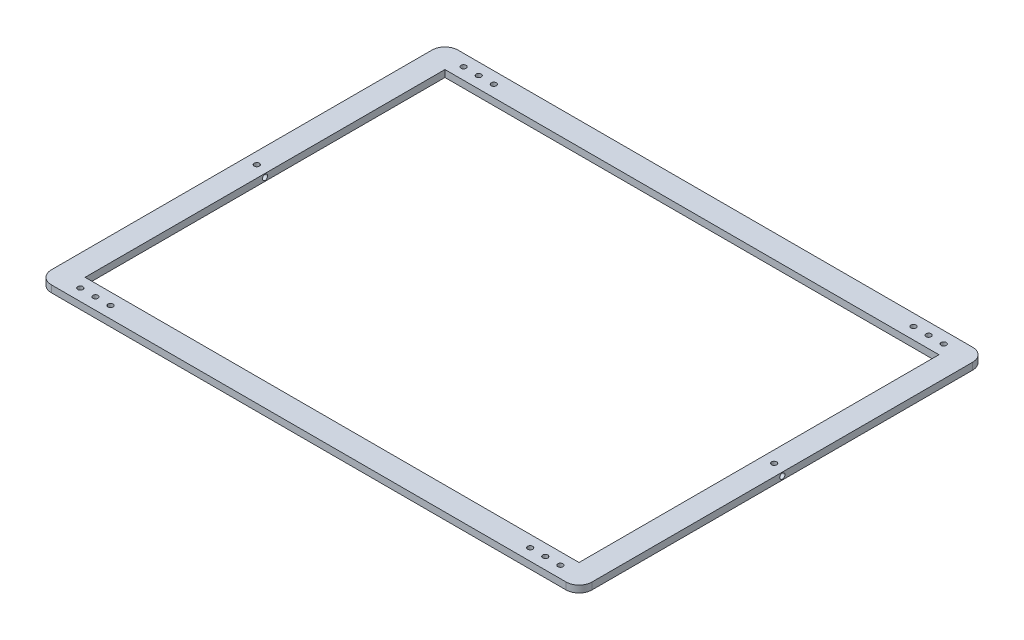
SolidWorks part; units mm, degrees
ref_plane "Спереди" through (0, 0, 0) normal (0, 0, 1) x (1, 0, 0)
ref_plane "Сверху" through (0, 0, 0) normal (0, 1, 0) x (1, 0, 0)
ref_plane "Справа" through (0, 0, 0) normal (1, 0, 0) x (0, 0, -1)
sketch "Эскиз1" plane through (0, 0, 0) normal (0, 1, 0) x (1, 0, 0)
  line L0 (0, 235) -> (0, -235) construction
  line L1 (-312.5, 235) -> (312.5, 235)
  line L2 (-312.5, 235) -> (-312.5, -235)
  line L3 (-312.5, -235) -> (312.5, -235)
  line L4 (312.5, 235) -> (312.5, -235)
  line L5 (-312.5, 0) -> (312.5, 0) construction
  line L6 (-285.5, 208) -> (285.5, 208)
  line L7 (285.5, 208) -> (285.5, -208)
  line L8 (-285.5, -208) -> (285.5, -208)
  line L9 (-285.5, 208) -> (-285.5, -208)
  point P9 (0, 0)
  point P10 (0, 0)
  point P11 (0, 0)
  dimension "D1" = 625
  dimension "D2" = 470
  dimension "D3" = 27
extrude "Бобышка-Вытянуть1" add sketch "Эскиз1" along normal mid plane 8
fillet "Скругление1" radius 15 4 edges at (312.5, 0, 235) (-312.5, 0, 235) (312.5, 0, -235) (-312.5, 0, -235)
ref_plane "Плоскость1" through (0, 0, -221.5) normal (0, 0, -1) x (-1, 0, 0)
ref_plane "Плоскость2" through (0, 0, 221.5) normal (0, 0, -1) x (-1, 0, 0)
ref_plane "Плоскость3" through (-299, 0, 0) normal (-1, 0, 0) x (0, 0, 1)
ref_plane "Плоскость4" through (299, 0, 0) normal (-1, 0, 0) x (0, 0, 1)
sketch "Эскиз2" plane through (0, 4, 0) normal (0, 1, 0) x (1, 0, 0)
  circle A0 centre (-277.5, -221.5) radius 3 construction
  circle A1 centre (-260, -221.5) radius 3 construction
  circle A2 centre (-242.5, -221.5) radius 3 construction
  circle A3 centre (242.5, -221.5) radius 3 construction
  circle A4 centre (260, -221.5) radius 3 construction
  circle A5 centre (277.5, -221.5) radius 3 construction
  circle A6 centre (242.5, 221.5) radius 3 construction
  circle A7 centre (260, 221.5) radius 3 construction
  circle A8 centre (277.5, 221.5) radius 3 construction
  circle A9 centre (-277.5, 221.5) radius 3 construction
  circle A10 centre (-260, 221.5) radius 3 construction
  circle A11 centre (-242.5, 221.5) radius 3 construction
  circle A12 centre (-277.5, -221.5) radius 3
  circle A13 centre (-260, -221.5) radius 3
  circle A14 centre (-242.5, -221.5) radius 3
  circle A15 centre (242.5, -221.5) radius 3
  circle A16 centre (260, -221.5) radius 3
  circle A17 centre (277.5, -221.5) radius 3
  circle A18 centre (242.5, 221.5) radius 3
  circle A19 centre (260, 221.5) radius 3
  circle A20 centre (277.5, 221.5) radius 3
  circle A21 centre (-277.5, 221.5) radius 3
  circle A22 centre (-260, 221.5) radius 3
  circle A23 centre (-242.5, 221.5) radius 3
extrude "Вырез-Вытянуть1" cut sketch "Эскиз2" against normal through all
sketch "Эскиз3" plane through (0, 0, 0) normal (1, 0, 0) x (0, 0, -1)
  circle A0 centre (0, 0) radius 3
  dimension "D1" = 6
extrude "Вырез-Вытянуть2" cut sketch "Эскиз3" against normal through all and the other way through all
sketch "Эскиз4" plane through (0, 4, 0) normal (0, 1, 0) x (1, 0, 0)
  line L0 (-299, 4.4) -> (-299, -4.4) construction
  line L1 (299, 4.4) -> (299, -4.4) construction
  circle A0 centre (-299, 4) radius 3
  circle A1 centre (299, 4) radius 3
  point P4 (0, 0)
  point P7 (0, 0)
  point P10 (0, 0)
  dimension "D1" = 6
  dimension "D2" = 4
extrude "Вырез-Вытянуть3" cut sketch "Эскиз4" against normal through all
